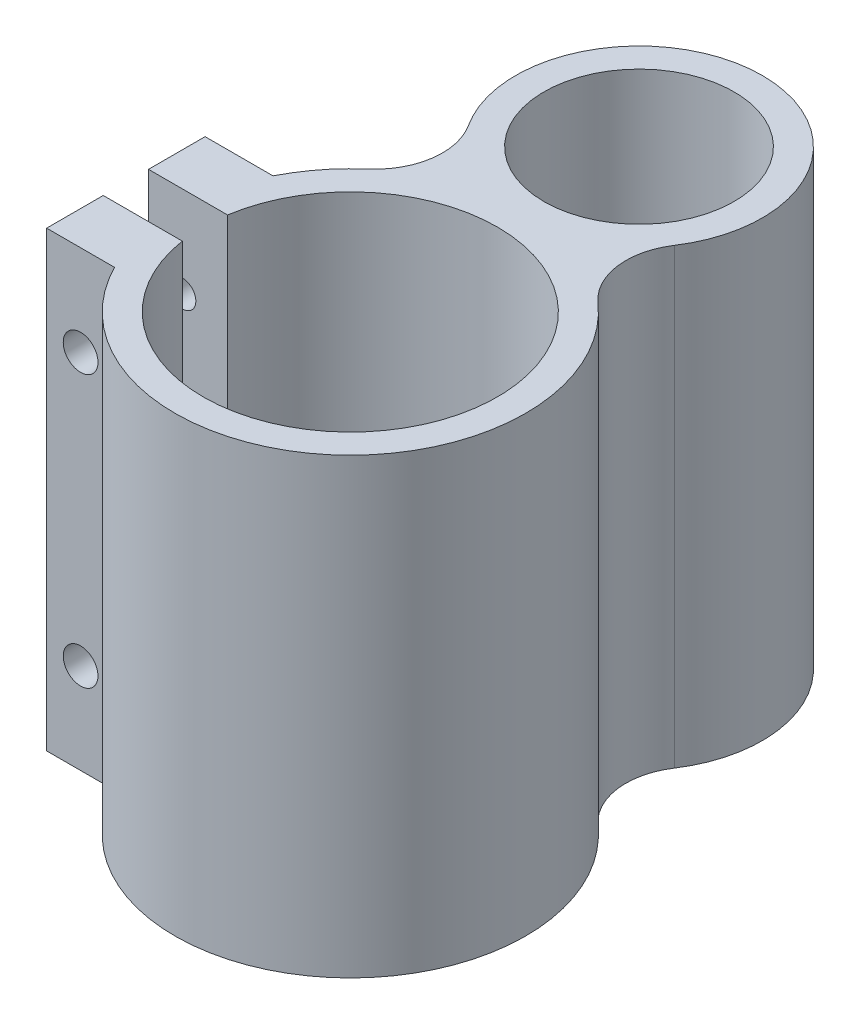
SolidWorks part; units mm, degrees
ref_plane "Front" through (0, 0, 0) normal (0, 0, 1) x (1, 0, 0)
ref_plane "Top" through (0, 0, 0) normal (0, 1, 0) x (1, 0, 0)
ref_plane "Right" through (0, 0, 0) normal (1, 0, 0) x (0, 0, -1)
ref_axis "Center Axis" through (0, 0, -88.99) along (0, 0, 1)
sketch "Sketch1" plane through (0, 0, 0) normal (0, 1, 0) x (1, 0, 0)
  line L1 (-3.6629, -20.8383) -> (-31.0082, -20.8383)
  line L2 (-3.6629, -20.8383) -> (-3.6629, -15.7583)
  line L3 (-3.6629, -15.7583) -> (-31.0082, -15.7583)
  line L4 (-31.0082, -20.8383) -> (-31.0082, -15.7583)
  line L5 (-3.6629, -20.8383) -> (-31.0082, -15.7583) construction
  line L6 (-3.6629, -15.7583) -> (-31.0082, -20.8383) construction
  line L7 (-17.3356, -15.7583) -> (-24.9556, -15.7583)
  line L8 (-17.3356, -15.7583) -> (-17.3356, -9.4083)
  line L9 (-17.3356, -9.4083) -> (-24.9556, -9.4083)
  line L10 (-24.9556, -15.7583) -> (-24.9556, -9.4083)
  line L11 (-17.3356, -20.8383) -> (-24.9556, -20.8383)
  line L12 (-17.3356, -20.8383) -> (-17.3356, -27.1883)
  line L13 (-17.3356, -27.1883) -> (-24.9556, -27.1883)
  line L14 (-24.9556, -20.8383) -> (-24.9556, -27.1883)
  circle A0 centre (0.3624, 13.9579) radius 10.668
  circle A1 centre (0.2277, -18.2983) radius 16.51
  circle A2 centre (0.3624, 13.9579) radius 13.843
  circle A3 centre (0.2277, -18.2983) radius 19.685
  point P4 (0.3624, 3.2899)
  point P9 (0.2277, -1.7883)
  point P11 (-17.3356, -18.2983)
  dimension "D1" = 21.336
  dimension "D2" = 33.02
  dimension "D3" = 5.08
  dimension "D5" = 5.08
  dimension "D6" = 6.35
  dimension "D7" = 7.62
  dimension "D4" = 3.175
extrude "Boss-Extrude1" add sketch "Sketch1" along normal blind 50.8 contours A2 A3 A1 | A3 A2 A0 | A2 A3 | L8 L7 L10 L9 | L12 L11 L14 L13 region at (-16.7107, 0, 21.3767) region at (0.3073, 0, -0.7731) region at (-7.433, 0, -24.9265)
fillet "Fillet1" radius 7.62 2 edges at (-4.1895, 25.4, -0.8847) (4.8049, 25.4, -0.8471)
sketch "Sketch2" plane through (0, 0, 20.8383) normal (0, 0, -1) x (-1, 0, 0)
  line L0 (17.3356, 50.8) -> (24.9556, 50.8) construction
  line L1 (24.9556, 25.4) -> (17.3356, 25.4) construction
  line L2 (24.9556, 50.8) -> (24.9556, 0) construction
  line L3 (17.3356, 50.8) -> (17.3356, 0) construction
  circle A0 centre (21.1456, 40.64) radius 1.95
  circle A1 centre (21.1456, 10.16) radius 1.95
  point P3 (21.1456, 50.8)
  dimension "D1" = 3.9
  dimension "D2" = 15.24
extrude "Cut-Extrude1" cut sketch "Sketch2" against normal through all
sketch "Sketch3" plane through (0, 0, 9.4083) normal (0, 0, -1) x (-1, 0, 0)
  circle A0 centre (21.1456, 40.64) radius 1.5
  circle A1 centre (21.1456, 10.16) radius 1.95
  circle A2 centre (21.1456, 10.16) radius 1.95
  circle A3 centre (21.1456, 40.64) radius 1.95
  circle A4 centre (21.1456, 40.64) radius 1.95
  circle A5 centre (21.1456, 10.16) radius 1.5
  dimension "D3" = 3
  dimension "D1" = 0
  dimension "D2" = 0
extrude "Cut-Extrude3" cut sketch "Sketch3" against normal up to next contours A5 | A0 region at (-21.1456, 10.16, 9.4083)
